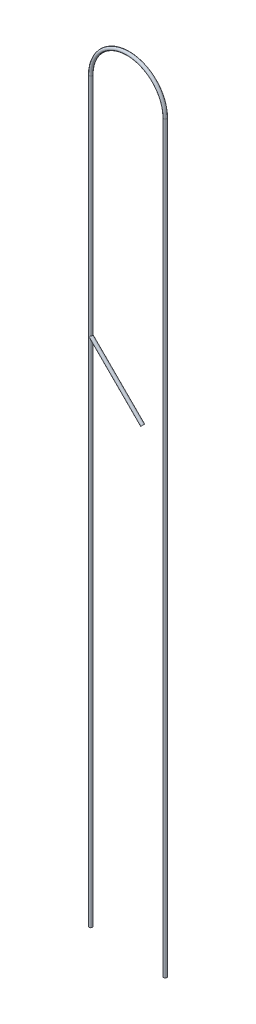
SolidWorks part; units mm, degrees
ref_plane "Front Plane" through (0, 0, 0) normal (0, 0, 1) x (1, 0, 0)
ref_plane "Top Plane" through (0, 0, 0) normal (0, 1, 0) x (1, 0, 0)
ref_plane "Right Plane" through (0, 0, 0) normal (1, 0, 0) x (0, 0, -1)
sketch3d "3DSketch1"
  line L0 (-21650.5611, -2258.4694, 40322.6002) -> (-21650.5611, -2253.4694, 40322.6002) construction
  line L1 (-21650.5611, -2253.4694, 40322.6002) -> (-21650.5611, 11528.5306, 40322.6002)
  line L2 (-21650.5611, 11528.5306, 40322.6002) -> (-23030.5611, 11528.5306, 40322.6002) construction
  line L3 (-22340.5611, 11528.5306, 40322.6002) -> (-22340.5611, 12218.5306, 40322.6002) construction
  line L4 (-23030.5611, 11528.5306, 40322.6002) -> (-23030.5611, -2137.13, 40322.6002)
  line L5 (-22901.5611, 11163.1904, 40199.9002) -> (-22901.5611, 11163.1904, 40322.6002) construction
  line L6 (-22901.5611, 12327.8571, 40199.9002) -> (-22901.5611, -2672.1429, 40199.9002) construction
  line L7 (-22901.5611, 11163.1904, 40322.6002) -> (-23030.5611, 11163.1904, 40322.6002) construction
  circle A0 centre (-21650.5611, -2258.4694, 40322.6002) radius 26.2509 construction
  arc A1 (-23030.5611, 11528.5306, 40322.6002) -> (-21650.5611, 11528.5306, 40322.6002) centre (-22340.5611, 11528.5306, 40322.6002) cw
  point P4 (-21650.5611, -2284.7203, 40322.6002)
  point P10 (-22340.5611, 11528.5306, 39632.6002)
  dimension "D1" = 690
  dimension "D2" = 129
sweep "Sweep-Thin1" add path "3DSketch1" circular profile diameter 60 parameters "D1"=3, "D3"=60
sketch3d "3DSketch2"
  line L0 (-23030.5611, 7347.9737, 40322.6002) -> (-22069.1183, 6386.5309, 40322.6002)
  line L1 (-23030.5611, 11528.5306, 40322.6002) -> (-23030.5611, -2137.13, 40322.6002) construction
  line L2 (-23030.5611, 7347.9737, 40322.6002) -> (-23030.5611, 6971.5252, 40322.6002) construction
  circle A0 centre (-22069.1183, 6386.5309, 40322.6002) radius 26.09 construction
  point P5 (-22069.1183, 6386.5309, 40322.6002)
  point P8 (-22050.6699, 6368.0825, 40322.6002)
  dimension "D1" = 45
sweep "Sweep-Thin2" add path "3DSketch2" circular profile diameter 60 parameters "D1"=3, "D3"=60
